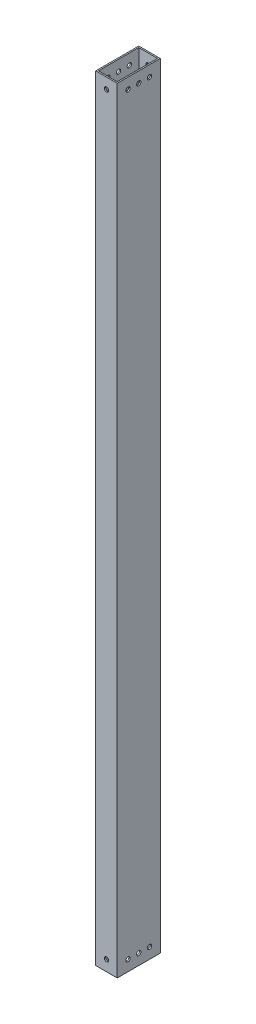
SolidWorks part; units mm, degrees
material "6061-T6 (SS)"
ref_plane "Front" through (0, 0, 0) normal (0, 0, 1) x (1, 0, 0)
ref_plane "Top" through (0, 0, 0) normal (0, 1, 0) x (1, 0, 0)
ref_plane "Right" through (0, 0, 0) normal (1, 0, 0) x (0, 0, -1)
sketch "Sketch1" plane through (0, 0, 0) normal (0, 1, 0) x (1, 0, 0)
  line L1 (12.7, 25.4) -> (-12.7, 25.4)
  line L2 (12.7, 25.4) -> (12.7, -25.4)
  line L3 (12.7, -25.4) -> (-12.7, -25.4)
  line L4 (-12.7, 25.4) -> (-12.7, -25.4)
  line L5 (12.7, 25.4) -> (-12.7, -25.4) construction
  line L6 (12.7, -25.4) -> (-12.7, 25.4) construction
  point P0 (0, 0)
  dimension "D1" = 25.4
  dimension "D2" = 50.8
extrude "Extrude-Thin1" add sketch "Sketch1" along normal blind 914.4 thin thin type one direction reverse wall 1.5875
sketch "Sketch4" plane through (-12.7, 0, 0) normal (-1, 0, 0) x (0, 0, 1)
  line L0 (-12.7, 901.7) -> (12.7, 901.7) construction
  line L2 (-25.4, 914.4) -> (25.4, 914.4) construction
  line L3 (-12.7, 12.7) -> (12.7, 12.7) construction
  line L5 (-25.4, 0) -> (25.4, 0) construction
  point P0 (-12.7, 901.7)
  point P2 (0, 901.7)
  point P4 (12.7, 901.7)
  point P15 (-12.7, 12.7)
  point P17 (0, 12.7)
  point P19 (12.7, 12.7)
  dimension "D1" = 12.7
  dimension "D2" = 12.7
  dimension "D3" = 12.7
  dimension "D4" = 12.7
hole_wizard "#10 Clearance Hole1" positions "Sketch4" profile "Sketch3" hole size "#10" standard "ANSI Inch" end condition through all
sketch "Sketch3" plane through (-12.7, 901.7, -12.7) normal (0, 1, 0) x (0, 0, 1)
  line L0 (0, 0) -> (0, 25.4)
  line L1 (0, 25.4) -> (2.5527, 25.4)
  line L2 (2.5527, 25.4) -> (2.5527, 0)
  line L5 (2.5527, 0) -> (0, 0)
  line L11 (0, -6.35) -> (0, 107.95) construction
  dimension "Thru Hole Dia." = 5.1054
  dimension "Thru Hole Depth" = 25.4
sketch "Sketch7" plane through (0, 0, 25.4) normal (0, 0, 1) x (1, 0, 0)
  line L0 (-12.7, 0) -> (12.7, 0) construction
  line L1 (-12.7, 914.4) -> (12.7, 914.4) construction
  point P0 (0, 901.7)
  point P2 (0, 12.7)
  dimension "D1" = 12.7
  dimension "D2" = 12.7
hole_wizard "#10 Clearance Hole2" positions "Sketch7" profile "Sketch6" hole size "#10" standard "ANSI Inch" end condition through all
sketch "Sketch6" plane through (0, 901.7, 25.4) normal (1, 0, 0) x (0, -1, 0)
  line L0 (0, 0) -> (0, 50.8)
  line L1 (0, 50.8) -> (2.5527, 50.8)
  line L2 (2.5527, 50.8) -> (2.5527, 0)
  line L5 (2.5527, 0) -> (0, 0)
  line L11 (0, -6.35) -> (0, 107.95) construction
  dimension "Thru Hole Dia." = 5.1054
  dimension "Thru Hole Depth" = 50.8
